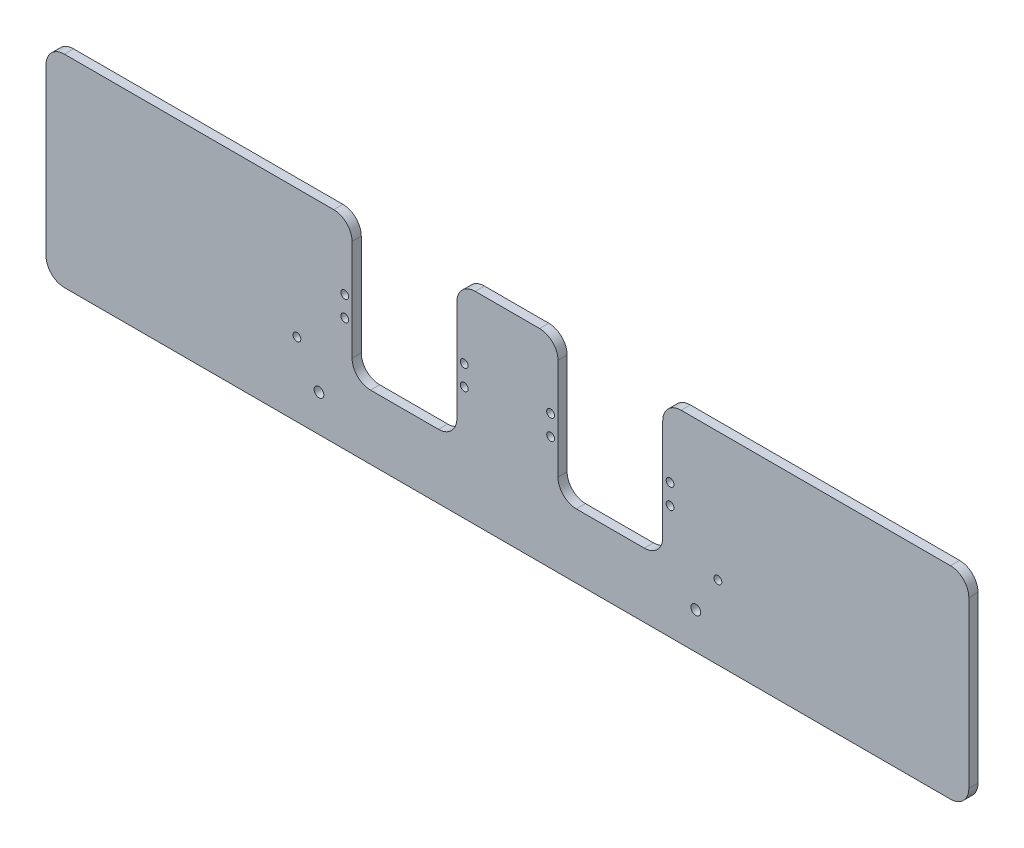
SolidWorks part; units mm, degrees
ref_plane "Front Plane" through (0, 0, 0) normal (0, 0, 1) x (1, 0, 0)
ref_plane "Top Plane" through (0, 0, 0) normal (0, 1, 0) x (1, 0, 0)
ref_plane "Right Plane" through (0, 0, 0) normal (1, 0, 0) x (0, 0, -1)
sketch "Sketch1" plane through (0, 0, 0) normal (0, 0, 1) x (1, 0, 0)
  line L0 (0, 0) -> (0, 110)
  line L1 (0, 110) -> (166.5, 110)
  line L2 (166.5, 110) -> (166.5, 35)
  line L3 (166.5, 35) -> (223.5, 35)
  line L4 (223.5, 35) -> (223.5, 110)
  line L5 (223.5, 110) -> (278.5, 110)
  line L6 (278.5, 110) -> (278.5, 35)
  line L7 (278.5, 35) -> (335.5, 35)
  line L8 (335.5, 35) -> (335.5, 110)
  line L9 (335.5, 110) -> (502, 110)
  line L10 (502, 110) -> (502, 0)
  line L11 (502, 0) -> (0, 0)
  dimension "D1" = 166.5
  dimension "D2" = 57
  dimension "D3" = 55
  dimension "D4" = 57
  dimension "124" = 166.5
  dimension "D6" = 110
  dimension "D7" = 75
  dimension "D8" = 75
  dimension "D9" = 75
  dimension "D10" = 75
extrude "Boss-Extrude1" add sketch "Sketch1" along normal blind 5
sketch "Sketch3" plane through (0, 0, 5) normal (0, 0, 1) x (1, 0, 0)
  line L0 (195, 35) -> (195, 133.0594) construction
  line L1 (223.5, 35) -> (166.5, 35) construction
  line L2 (251, 110) -> (251, 1.7727) construction
  line L3 (278.5, 110) -> (223.5, 110) construction
  line L4 (166.5, 35) -> (166.5, 110) construction
  circle A0 centre (162.5, 73) radius 2.125
  circle A1 centre (162.5, 62) radius 2.125
  circle A2 centre (227.5, 62) radius 2.125
  circle A3 centre (227.5, 73) radius 2.125
  circle A4 centre (274.5, 73) radius 2.125
  circle A5 centre (274.5, 62) radius 2.125
  circle A6 centre (339.5, 62) radius 2.125
  circle A7 centre (339.5, 73) radius 2.125
  dimension "D1" = 4.25
  dimension "D2" = 4.25
  dimension "D3" = 27
  dimension "D4" = 38
  dimension "D5" = 4
  dimension "D6" = 4
extrude "Cut-Extrude1" cut sketch "Sketch3" against normal blind 10
fillet "Fillet1" radius 10 4 edges at (502, 0, 2.5) (502, 110, 2.5) (0, 0, 2.5) (0, 110, 2.5)
sketch "Sketch4" plane through (0, 0, 5) normal (0, 0, 1) x (1, 0, 0)
  line L0 (166.5, 35) -> (166.5, 110) construction
  line L1 (10, 0) -> (492, 0) construction
  line L2 (251, 110) -> (251, 0) construction
  line L3 (278.5, 110) -> (223.5, 110) construction
  line L4 (0, 100) -> (0, 10) construction
  circle A1 centre (148.5, 20) radius 2.65
  circle A2 centre (353.5, 20) radius 2.65
  dimension "D3" = 5.3
  dimension "D1" = 18
  dimension "D2" = 20
extrude "Cut-Extrude2" cut sketch "Sketch4" against normal blind 10
sketch "Sketch5" plane through (0, 0, 5) normal (0, 0, 1) x (1, 0, 0)
  line L0 (10, 0) -> (492, 0) construction
  line L1 (335.5, 110) -> (335.5, 35) construction
  line L2 (251, 110) -> (251, 0) construction
  line L3 (278.5, 110) -> (223.5, 110) construction
  line L4 (502, 10) -> (502, 100) construction
  circle A0 centre (365.5, 40) radius 2.125
  circle A1 centre (136.5, 40) radius 2.125
  dimension "D1" = 4.25
  dimension "D2" = 40
  dimension "D3" = 30
extrude "Cut-Extrude3" cut sketch "Sketch5" against normal blind 10
fillet "Fillet2" radius 10 8 edges at (335.5, 35, 2.5) (335.5, 110, 2.5) (278.5, 110, 2.5) (278.5, 35, 2.5) (223.5, 35, 2.5) (223.5, 110, 2.5) (166.5, 35, 2.5) (166.5, 110, 2.5)
